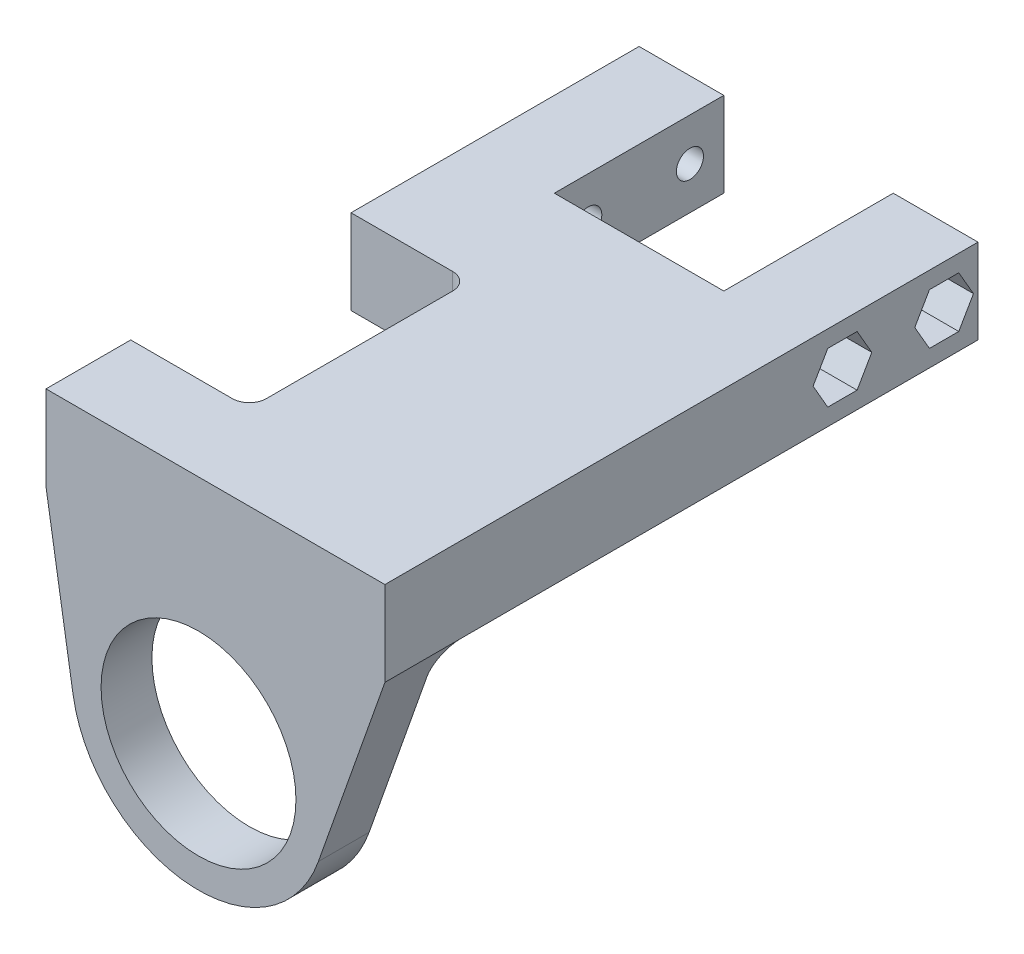
SolidWorks part; units mm, degrees
ref_plane "Top Plane" through (0, 0, 0) normal (0, 0, 1) x (1, 0, 0)
ref_plane "Right Plane" through (0, 0, 0) normal (0, 1, 0) x (1, 0, 0)
ref_plane "Front Plane" through (0, 0, 0) normal (1, 0, 0) x (0, 0, -1)
sketch "Sketch1" plane through (0, 0, 0) normal (0, 0, 1) x (1, 0, 0)
  line L0 (0, 0) -> (0, 27.25) construction
  line L1 (22, 27.25) -> (22, 17.25)
  line L2 (-18, 27.25) -> (22, 27.25)
  line L3 (-18, 27.25) -> (-18, 17.25)
  line L4 (22, 17.25) -> (14.1439, -4.9951)
  line L5 (-18, 17.25) -> (-14.8058, -2.406)
  arc A0 (-14.8058, -2.406) -> (14.1439, -4.9951) centre (0, 0) ccw construction
  circle A1 centre (0, 0) radius 11 construction
  circle A2 centre (0, 0) radius 4 construction
  arc A3 (-14.8058, -2.406) -> (14.1439, -4.9951) centre (0, 0) ccw
  dimension "D1" = 30
  dimension "D2" = 22
  dimension "D3" = 8
  dimension "D6" = 10
  dimension "D4" = 27.25
  dimension "D5" = 40
  dimension "D7" = 18
extrude "Boss-Extrude1" add sketch "Sketch1" along normal blind 6
sketch "Sketch2" plane through (0, 0, 6) normal (0, 0, 1) x (1, 0, 0)
  circle A2 centre (0, 0) radius 11.5
  circle A3 centre (0, 0) radius 11.5
  dimension "D1" = 0.5
extrude "Cut-Extrude1" cut sketch "Sketch2" against normal through all
sketch "Sketch3" plane through (0, 0, 0) normal (0, 0, -1) x (-1, 0, 0)
  line L0 (18, 27.25) -> (-22, 27.25) construction
  line L1 (-22, 27.25) -> (-12, 27.25) construction
  line L2 (-22, 27.25) -> (-22, 17.25) construction
  line L3 (-22, 17.25) -> (-12, 17.25) construction
  line L4 (-12, 27.25) -> (-12, 17.25) construction
  line L5 (8, 27.25) -> (18, 27.25) construction
  line L6 (8, 27.25) -> (8, 17.25) construction
  line L7 (8, 17.25) -> (18, 17.25) construction
  line L8 (18, 27.25) -> (18, 17.25) construction
  line L9 (-12, 22.25) -> (8, 22.25) construction
  line L11 (-2, 22.25) -> (-2, 27.25) construction
  line L13 (-22, 27.25) -> (18, 27.25)
  line L14 (-22, 27.25) -> (-22, 17.25)
  line L15 (-22, 17.25) -> (18, 17.25)
  line L16 (18, 27.25) -> (18, 17.25)
  point P12 (-2, 22.25)
  dimension "D1" = 20
extrude "Boss-Extrude2" add sketch "Sketch3" along normal blind 44
sketch "Sketch4" plane through (0, 0, -44) normal (0, 0, -1) x (-1, 0, 0)
  line L1 (-22, 27.25) -> (-12, 27.25)
  line L2 (-22, 27.25) -> (-22, 17.25)
  line L3 (-22, 17.25) -> (-12, 17.25)
  line L4 (-12, 27.25) -> (-12, 17.25)
  line L5 (8, 27.25) -> (18, 27.25)
  line L6 (8, 27.25) -> (8, 17.25)
  line L7 (8, 17.25) -> (18, 17.25)
  line L8 (18, 27.25) -> (18, 17.25)
extrude "Boss-Extrude3" add sketch "Sketch4" along normal blind 20
fillet "Fillet1" radius 3 1 edges at (2, 17.25, 0)
sketch "Sketch5" plane through (12, 0, 0) normal (-1, 0, 0) x (0, 0, 1)
  line L0 (-64, 22.25) -> (-44, 22.25) construction
  line L1 (-64, 17.25) -> (-64, 27.25) construction
  line L2 (-44, 17.25) -> (-44, 27.25) construction
  line L3 (-54, 27.25) -> (-54, 22.25) construction
  line L4 (-64, 27.25) -> (-44, 27.25) construction
  circle A0 centre (-60, 22.25) radius 1.75
  circle A1 centre (-48, 22.25) radius 1.75
  dimension "D1" = 3.5
  dimension "D2" = 12
hole_wizard "CBORE for M3 Hex Socket Head Cap Screw1" positions "Sketch6" profile "Sketch7" counterbore size "M3" standard "ISO" end condition through all
sketch "Sketch6" plane through (-18, 0, 0) normal (-1, 0, 0) x (0, 0, 1)
  point P0 (-60, 22.25)
  point P3 (-48, 22.25)
sketch "Sketch7" plane through (-18, 22.25, -60) normal (0, 1, 0) x (0, 0, 1)
  line L0 (0, 0) -> (0, 40)
  line L1 (0, 40) -> (1.6, 40)
  line L3 (1.6, 40) -> (1.6, 3.4)
  line L4 (1.6, 3.4) -> (3.25, 3.4)
  line L5 (3.25, 3.4) -> (3.25, 0)
  line L7 (3.25, 0) -> (0, 0)
  line L11 (0, -6.35) -> (0, 107.95) construction
  dimension "Thru Hole Dia." = 3.2
  dimension "Thru Hole Depth" = 40
  dimension "C'Bore Dia." = 6.5
  dimension "C'Bore Depth" = 3.4
sketch "Sketch8" plane through (22, 0, 0) normal (1, 0, 0) x (0, 0, -1)
  line L1 (49.7321, 25.25) -> (46.2679, 25.25)
  line L2 (46.2679, 25.25) -> (44.5359, 22.25)
  line L3 (44.5359, 22.25) -> (46.2679, 19.25)
  line L4 (46.2679, 19.25) -> (49.7321, 19.25)
  line L5 (49.7321, 19.25) -> (51.4641, 22.25)
  line L6 (51.4641, 22.25) -> (49.7321, 25.25)
  line L7 (58.2679, 25.25) -> (56.5359, 22.25)
  line L8 (56.5359, 22.25) -> (58.2679, 19.25)
  line L9 (58.2679, 19.25) -> (61.7321, 19.25)
  line L10 (61.7321, 19.25) -> (63.4641, 22.25)
  line L11 (63.4641, 22.25) -> (61.7321, 25.25)
  line L12 (61.7321, 25.25) -> (58.2679, 25.25)
  circle A0 centre (48, 22.25) radius 3 construction
  circle A1 centre (60, 22.25) radius 3 construction
  dimension "D1" = 6
extrude "Cut-Extrude3" cut sketch "Sketch8" against normal offset from surface (6 mm away) 4 up to face at (12, 22.25, -61.6)
sketch "Sketch9" plane through (0, 27.25, 0) normal (0, 1, 0) x (1, 0, 0)
  line L0 (-18, -6) -> (-18, 64) construction
  line L1 (-18, 30) -> (-4, 30)
  line L2 (-18, 30) -> (-18, 4)
  line L3 (-18, 4) -> (-4, 4)
  line L4 (-4, 30) -> (-4, 4)
  line L5 (22, -6) -> (-18, -6) construction
  dimension "D1" = 36
  dimension "D2" = 10
  dimension "D3" = 14
extrude "Cut-Extrude4" cut sketch "Sketch9" against normal through all
fillet "Fillet2" radius 2 2 edges at (-4, 22.25, -4) (-4, 22.25, -30)
